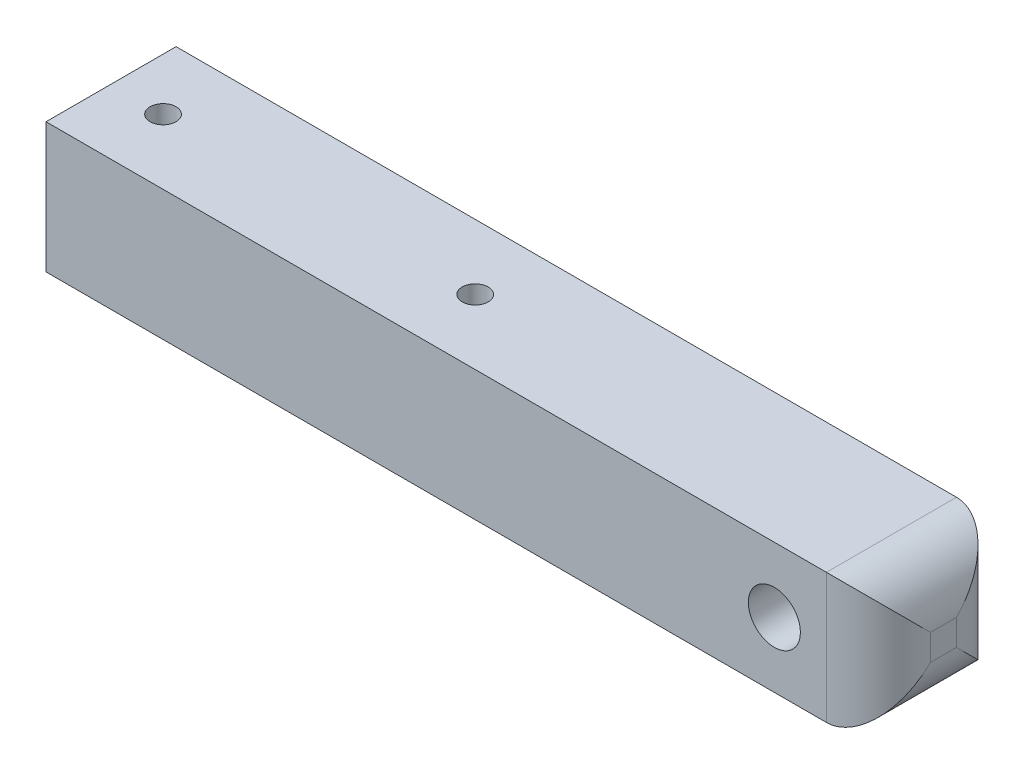
SolidWorks part; units mm, degrees
material "ABS"
ref_plane "Front Plane" through (0, 0, 0) normal (0, 0, 1) x (1, 0, 0)
ref_plane "Top Plane" through (0, 0, 0) normal (0, 1, 0) x (1, 0, 0)
ref_plane "Right Plane" through (0, 0, 0) normal (1, 0, 0) x (0, 0, -1)
sketch "Sketch1" plane through (0, 0, 0) normal (0, 0, 1) x (1, 0, 0)
  line L0 (0, 0) -> (101.6, 0)
  line L1 (101.6, 0) -> (101.6, 31.75)
  line L2 (101.6, 31.75) -> (-101.6, 31.75)
  line L3 (-101.6, 31.75) -> (-101.6, 0)
  line L4 (-101.6, 0) -> (0, 0)
  dimension "D1" = 31.75
  dimension "D2" = 203.2
extrude "Boss-Extrude1" add sketch "Sketch1" along normal mid plane 31.75
sketch "Sketch2" plane through (-101.6, 0, 0) normal (-1, 0, 0) x (0, 0, 1)
  line L0 (0, 4.9711) -> (-8.9803, 13.9513)
  line L1 (-8.9803, 13.9513) -> (-9.8783, 13.0533)
  line L2 (-9.8783, 13.0533) -> (0, 3.175)
  line L3 (0, 3.175) -> (9.8783, 13.0533)
  line L4 (9.8783, 13.0533) -> (8.9803, 13.9513)
  line L5 (8.9803, 13.9513) -> (0, 4.9711)
  line L6 (-11.3146, 0) -> (21.0706, 0) construction
  line L7 (-15.875, 31.75) -> (-15.875, 0) construction
  line L8 (-9.8783, 13.0533) -> (-15.875, 13.0533) construction
  line L9 (9.8783, 13.0533) -> (15.875, 13.0533) construction
  line L10 (15.875, 31.75) -> (15.875, 0) construction
  dimension "D1" = 1.27
  dimension "D2" = 3.175
  dimension "D3" = 12.7
extrude "Cut-Extrude1" cut sketch "Sketch2" against normal blind 152.4
hole_wizard "1/2 (0.5) Diameter Hole1" positions "Sketch3" profile "Sketch4" hole size "1/2" standard "ANSI Inch" end condition through all
sketch "Sketch3" plane through (0, 0, 15.875) normal (0, 0, 1) x (1, 0, 0)
  line L0 (-101.6, 31.75) -> (-101.6, 0) construction
  line L1 (-101.6, 15.875) -> (162.3719, 15.875) construction
  point P0 (76.2, 15.875)
  dimension "D1" = 177.8
sketch "Sketch4" plane through (76.2, 15.875, 15.875) normal (1, 0, 0) x (0, -1, 0)
  line L0 (0, 0) -> (0, 31.75)
  line L1 (0, 31.75) -> (6.35, 31.75)
  line L2 (6.35, 31.75) -> (6.35, 0)
  line L5 (6.35, 0) -> (0, 0)
  line L11 (0, -6.35) -> (0, 107.95) construction
  dimension "Thru Hole Dia." = 12.7
  dimension "Thru Hole Depth" = 31.75
hole_wizard "1/4 (0.25) Diameter Hole1" positions "Sketch5" profile "Sketch6" hole size "1/4" standard "ANSI Inch" end condition through all
sketch "Sketch5" plane through (0, 31.75, 0) normal (0, 1, 0) x (1, 0, 0)
  line L0 (-101.6, -15.875) -> (-101.6, 15.875) construction
  point P0 (-88.9, 0)
  point P2 (-12.7, 0)
  dimension "D1" = 12.7
  dimension "D2" = 76.2
sketch "Sketch6" plane through (-88.9, 31.75, 0) normal (1, 0, 0) x (0, 0, 1)
  line L0 (0, 0) -> (0, 31.75)
  line L1 (0, 31.75) -> (3.175, 31.75)
  line L2 (3.175, 31.75) -> (3.175, 0)
  line L5 (3.175, 0) -> (0, 0)
  line L11 (0, -6.35) -> (0, 107.95) construction
  dimension "Thru Hole Dia." = 6.35
  dimension "Thru Hole Depth" = 31.75
fillet "Fillet1" radius 12.7 4 edges at (101.6, 0, 0) (101.6, 15.875, -15.875) (101.6, 31.75, 0) (101.6, 15.875, 15.875)
